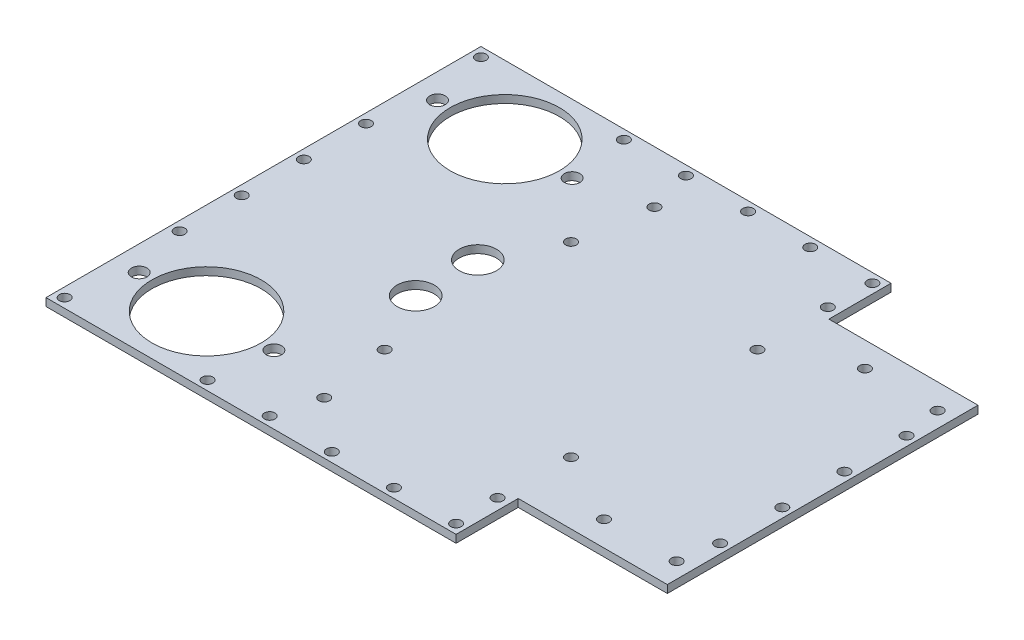
SolidWorks part; units mm, degrees
ref_plane "Front Plane" through (0, 0, 0) normal (0, 0, 1) x (1, 0, 0)
ref_plane "Top Plane" through (0, 0, 0) normal (0, 1, 0) x (1, 0, 0)
ref_plane "Right Plane" through (0, 0, 0) normal (1, 0, 0) x (0, 0, -1)
sketch "Sketch1" plane through (0, 0, 0) normal (0, 1, 0) x (1, 0, 0)
  line L1 (-217.8874, 70.6405) -> (10.7126, 70.6405)
  line L2 (-217.8874, 70.6405) -> (-217.8874, -107.1595)
  line L3 (-217.8874, -107.1595) -> (10.7126, -107.1595)
  line L4 (10.7126, 70.6405) -> (10.7126, -107.1595)
  dimension "D1" = 228.6
  dimension "D2" = 177.8
extrude "Boss-Extrude1" add sketch "Sketch1" along normal blind 3.175
sketch "Sketch2" plane through (0, 3.175, 0) normal (0, 1, 0) x (1, 0, 0)
  line L0 (-217.8874, -107.1595) -> (10.7126, -107.1595) construction
  line L1 (10.7126, -107.1595) -> (-50.2474, -107.1595)
  line L2 (10.7126, -107.1595) -> (10.7126, -81.7595)
  line L3 (10.7126, -81.7595) -> (-50.2474, -81.7595)
  line L4 (-50.2474, -107.1595) -> (-50.2474, -81.7595)
  line L5 (10.7126, -107.1595) -> (10.7126, 70.6405) construction
  line L6 (10.7126, 70.6405) -> (-217.8874, 70.6405) construction
  line L7 (10.7126, 70.6405) -> (-50.2474, 70.6405)
  line L8 (10.7126, 70.6405) -> (10.7126, 45.2405)
  line L9 (10.7126, 45.2405) -> (-50.2474, 45.2405)
  line L10 (-50.2474, 70.6405) -> (-50.2474, 45.2405)
  line L11 (-217.8874, 70.6405) -> (-217.8874, -107.1595) construction
  circle A0 centre (4.3626, 35.0805) radius 2.1717
  circle A1 centre (-25.3554, 35.0805) radius 2.1717
  circle A2 centre (4.3626, -71.5995) radius 2.1717
  circle A3 centre (-25.3554, -71.5995) radius 2.1717
  circle A4 centre (-207.7274, 42.7005) radius 3.175
  circle A5 centre (-152.6602, 42.7005) radius 3.175
  circle A6 centre (-180.1938, 42.7005) radius 22.352
  circle A7 centre (-207.7274, -79.2195) radius 3.175
  circle A8 centre (-180.1938, -79.2195) radius 22.352
  circle A9 centre (-152.6602, -79.2195) radius 3.175
  circle A10 centre (-54.6924, 49.2405) radius 2.1717
  circle A11 centre (-125.5584, 49.2405) radius 2.1717
  circle A12 centre (-125.5584, -85.7595) radius 2.1717
  circle A13 centre (-54.6924, -85.7595) radius 2.1717
  circle A14 centre (-54.0574, 66.8305) radius 2.159
  circle A15 centre (-54.0574, -103.3495) radius 2.159
  circle A16 centre (-214.0774, 66.8305) radius 2.159
  circle A17 centre (-214.0774, -103.3495) radius 2.1717
  circle A18 centre (-79.4574, 66.8305) radius 2.1717
  circle A19 centre (-104.8574, 66.8305) radius 2.1717
  circle A20 centre (-130.2574, 66.8305) radius 2.1717
  circle A21 centre (-155.6574, 66.8305) radius 2.1717
  circle A22 centre (-79.4574, -103.3495) radius 2.1717
  circle A23 centre (-104.8574, -103.3495) radius 2.1717
  circle A24 centre (-130.2574, -103.3495) radius 2.1717
  circle A25 centre (-155.6574, -103.3495) radius 2.1717
  circle A26 centre (-214.0774, 19.8405) radius 2.1717
  circle A27 centre (-214.0774, -5.5595) radius 2.1717
  circle A28 centre (-214.0774, -30.9595) radius 2.1717
  circle A29 centre (-214.0774, -56.3595) radius 2.1717
  circle A30 centre (-130.2574, 19.8405) radius 2.1717
  circle A31 centre (-130.2574, -56.3595) radius 2.1717
  circle A32 centre (6.9026, 19.8405) radius 2.1717
  circle A33 centre (6.9026, -5.5595) radius 2.1717
  circle A34 centre (6.9026, -30.9595) radius 2.1717
  circle A35 centre (6.9026, -56.3595) radius 2.1717
  circle A36 centre (-54.0574, 19.8405) radius 2.1717
  circle A37 centre (-54.0574, -56.3595) radius 2.1717
  circle A38 centre (-142.9574, -30.9595) radius 7.62
  circle A39 centre (-142.9574, -5.5595) radius 7.62
  dimension "D5" = 6.35
  dimension "D7" = 10.16
  dimension "D9" = 6.35
  dimension "D11" = 29.718
  dimension "D13" = 27.94
  dimension "D15" = 55.0672
  dimension "D17" = 10.16
  dimension "D19" = 27.5336
  dimension "D20" = 55.0672
  dimension "D21" = 21.4
  dimension "D22" = 70.866
  dimension "D24" = 135
  dimension "D25" = 3.81
  dimension "D27" = 3.81
  dimension "D30" = 3.81
  dimension "D32" = 3.81
  dimension "D34" = 25.4
  dimension "D35" = 25.4
  dimension "D38" = 25.4
  dimension "D40" = 25.4
  dimension "D42" = 3.81
  dimension "D44" = 25.4
  dimension "D46" = 25.4
  dimension "D48" = 25.4
  dimension "D50" = 46.99
  dimension "D52" = 25.4
  dimension "D53" = 25.4
  dimension "D54" = 25.4
  dimension "D55" = 46.99
  dimension "D57" = 46.99
  dimension "D59" = 3.81
  dimension "D60" = 25.4
  dimension "D61" = 25.4
  dimension "D62" = 25.4
  dimension "D66" = 46.99
  dimension "D68" = 60.96
  dimension "D70" = 71.12
  dimension "D71" = 71.12
  dimension "D1" = 25.4
  dimension "D2" = 60.96
  dimension "D3" = 60.96
  dimension "D4" = 25.4
  dimension "D6" = 10.16
  dimension "D8" = 29.718
  dimension "D10" = 10.16
  dimension "D12" = 10.16
  dimension "D14" = 10.16
  dimension "D16" = 27.5336
  dimension "D18" = 27.94
  dimension "D23" = 4.445
  dimension "D26" = 3.81
  dimension "D28" = 3.81
  dimension "D29" = 70.866
  dimension "D31" = 3.81
  dimension "D33" = 3.81
  dimension "D36" = 3.81
  dimension "D37" = 3.81
  dimension "D39" = 3.81
  dimension "D41" = 3.81
  dimension "D43" = 25.4
  dimension "D45" = 3.81
  dimension "D47" = 3.81
  dimension "D49" = 3.81
  dimension "D51" = 3.81
  dimension "D56" = 83.82
  dimension "D58" = 83.82
  dimension "D63" = 3.81
  dimension "D64" = 3.81
  dimension "D65" = 3.81
  dimension "D67" = 60.96
  dimension "D69" = 46.99
extrude "Cut-Extrude1" cut sketch "Sketch2" against normal blind 3.175
